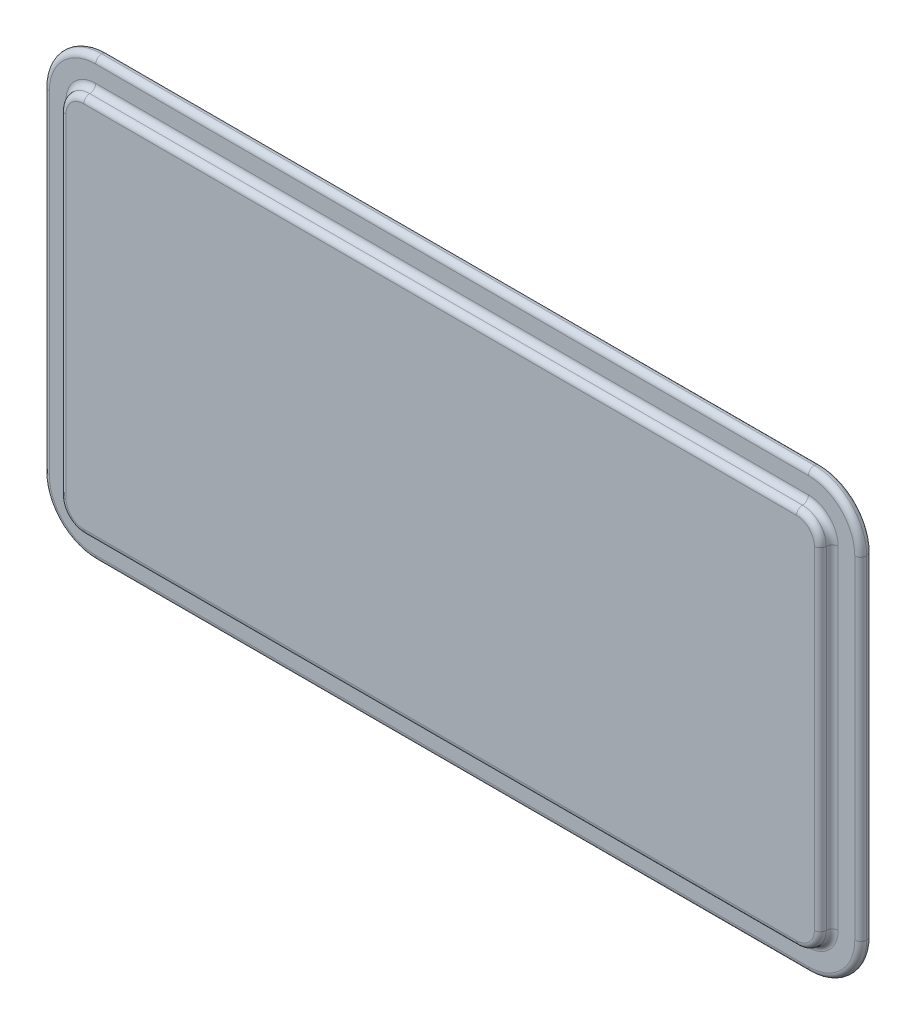
SolidWorks part; units mm, degrees
material "Стекло кварцевое прозрачное"
ref_plane "Спереди" through (0, 0, 0) normal (0, 0, 1) x (1, 0, 0)
ref_plane "Сверху" through (0, 0, 0) normal (0, 1, 0) x (1, 0, 0)
ref_plane "Справа" through (0, 0, 0) normal (1, 0, 0) x (0, 0, -1)
sketch "Sketch3" plane through (0, 0, 0) normal (0, 0, 1) x (1, 0, 0)
  line L13 (-150, 80) -> (150, 80)
  line L14 (-160, 70) -> (-160, -70)
  line L15 (-150, -80) -> (150, -80)
  line L24 (160, 70) -> (160, -70)
  line L25 (-160, 80) -> (160, -80) construction
  line L26 (-160, -80) -> (160, 80) construction
  arc A12 (150, -80) -> (160, -70) centre (150, -70) ccw
  arc A13 (150, 80) -> (160, 70) centre (150, 70) cw
  arc A14 (-160, -70) -> (-150, -80) centre (-150, -70) ccw
  arc A15 (-150, 80) -> (-160, 70) centre (-150, 70) ccw
  point P0 (0, 0)
  dimension "D4" = 10
  dimension "D2" = 320
  dimension "D3" = 160
extrude "Boss-Extrude2" add sketch "Sketch3" along normal blind 5
sketch "Sketch4" plane through (0, 0, 0) normal (0, 0, -1) x (-1, 0, 0)
  line L8 (150, 92) -> (-150, 92)
  line L9 (-172, 70) -> (-172, -70)
  line L10 (-150, -92) -> (150, -92)
  line L11 (172, -70) -> (172, 70)
  line L12 (150, 92) -> (-150, 92)
  line L13 (-172, 70) -> (-172, -70)
  line L14 (-150, -92) -> (150, -92)
  line L15 (172, -70) -> (172, 70)
  arc A8 (172, 70) -> (150, 92) centre (150, 70) ccw
  arc A9 (-150, 92) -> (-172, 70) centre (-150, 70) ccw
  arc A10 (-172, -70) -> (-150, -92) centre (-150, -70) ccw
  arc A11 (150, -92) -> (172, -70) centre (150, -70) ccw
  arc A12 (172, 70) -> (150, 92) centre (150, 70) ccw
  arc A13 (-150, 92) -> (-172, 70) centre (-150, 70) ccw
  arc A14 (-172, -70) -> (-150, -92) centre (-150, -70) ccw
  arc A15 (150, -92) -> (172, -70) centre (150, -70) ccw
  dimension "D1" = 12
extrude "Boss-Extrude3" add sketch "Sketch4" along normal blind 5
fillet "Fillet4" radius 2.5 32 edges at (-157.0711, 77.0711, 5) (0, 80, 5) (157.0711, 77.0711, 5) (160, 0, 5) (157.0711, -77.0711, 5) (-160, 0, 5) (0, -80, 5) (-157.0711, -77.0711, 5) (-157.0711, 77.0711, 0) (0, 80, 0) (157.0711, 77.0711, 0) (160, 0, 0) (157.0711, -77.0711, 0) (0, -80, 0) (-157.0711, -77.0711, 0) (-160, 0, 0) (-165.5563, -85.5563, -5) (0, -92, -5) (165.5563, -85.5563, -5) (172, 0, -5) (165.5563, 85.5563, -5) (0, 92, -5) (-165.5563, 85.5563, -5) (-165.5563, -85.5563, 0) (0, -92, 0) (165.5563, -85.5563, 0) (172, 0, 0) (165.5563, 85.5563, 0) (0, 92, 0) (-165.5563, 85.5563, 0) (-172, 0, -5) (-172, 0, 0)
